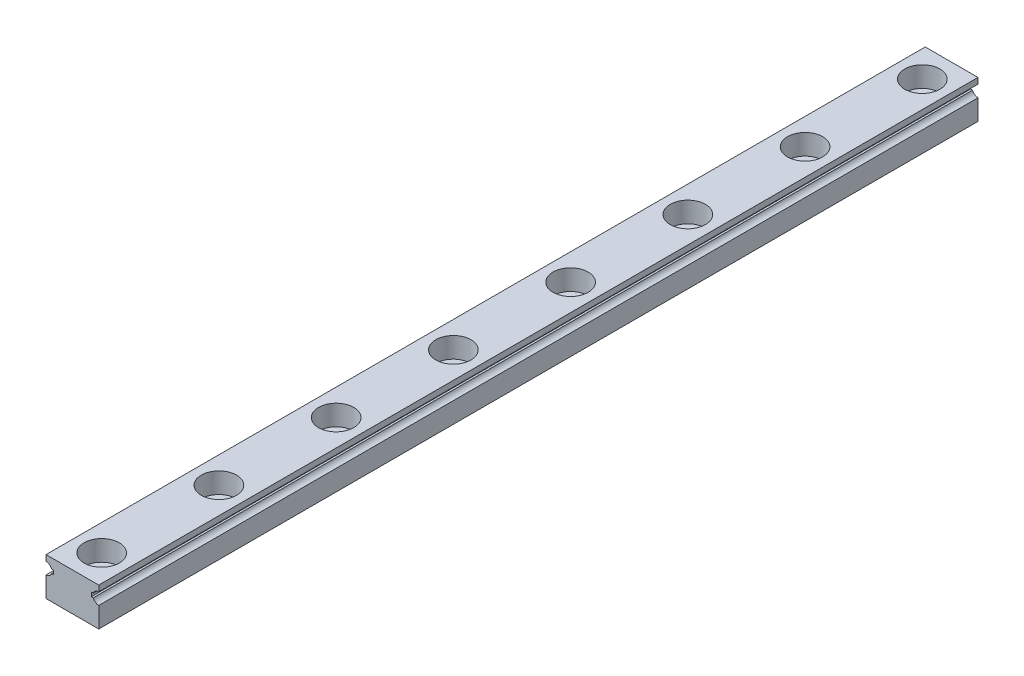
SolidWorks part; units mm, degrees
ref_plane "Спереди" through (0, 0, 0) normal (0, 0, 1) x (1, 0, 0)
ref_plane "Сверху" through (0, 0, 0) normal (0, 1, 0) x (1, 0, 0)
ref_plane "Справа" through (0, 0, 0) normal (1, 0, 0) x (0, 0, -1)
sketch "Sketch1" plane through (0, 0, 0) normal (0, 0, 1) x (1, 0, 0)
  line L0 (0, 0) -> (0, 5.7299) construction
  line L1 (-4.5, -3.25) -> (4.5, -3.25)
  line L2 (-4.5, -3.25) -> (-4.5, 0.25)
  line L3 (-4.5, 3.25) -> (4.5, 3.25)
  line L4 (4.5, -3.25) -> (4.5, 0.25)
  line L5 (-4.5, -3.25) -> (4.5, 3.25) construction
  line L6 (-4.5, 3.25) -> (4.5, -3.25) construction
  line L7 (-4.5, 2.25) -> (-4.5, 3.25)
  line L8 (-3.564, 0.898) -> (-3.2351, 0.898)
  line L9 (3.564, 0.898) -> (3.2351, 0.898)
  line L10 (-3.564, 1.602) -> (-3.2351, 1.602)
  line L11 (-3.2351, 0.898) -> (-3.2351, 1.602)
  line L12 (3.2351, 0.898) -> (3.2351, 1.602)
  line L13 (3.564, 1.602) -> (3.2351, 1.602)
  line L14 (4.5, 2.25) -> (4.5, 3.25)
  arc A0 (-3.564, 1.602) -> (-4.5, 2.25) centre (-4.5, 1.25) ccw
  arc A1 (-4.5, 0.25) -> (-3.564, 0.898) centre (-4.5, 1.25) ccw
  arc A2 (4.5, 0.25) -> (3.564, 0.898) centre (4.5, 1.25) cw
  arc A3 (3.564, 1.602) -> (4.5, 2.25) centre (4.5, 1.25) cw
  point P0 (0, 0)
  dimension "D3" = 1
  dimension "D1" = 9
  dimension "D2" = 6.5
  dimension "D4" = 2
extrude "Extrude1" add sketch "Sketch1" along normal blind 150
sketch "Sketch2" plane through (0, 3.25, 0) normal (0, 1, 0) x (1, 0, 0)
  line L0 (4.5, 0) -> (-4.5, 0) construction
  circle A0 centre (0, -5) radius 1.75
  circle A1 centre (0, -5) radius 3
  dimension "D1" = 3.5
  dimension "D2" = 6
  dimension "D3" = 5
extrude "Extrude2" cut sketch "Sketch2" against normal blind 3.5 contours A1
extrude "Extrude3" cut sketch "Sketch" against normal through all contours A0
sketch "Sketch" plane through (0, 3.25, 0) normal (0, 1, 0) x (1, 0, 0) same geometry as "Sketch2"
pattern_linear "LPattern1" count 13 spacing 20 along (0, 0, 1) of "Extrude2", "Extrude3"
